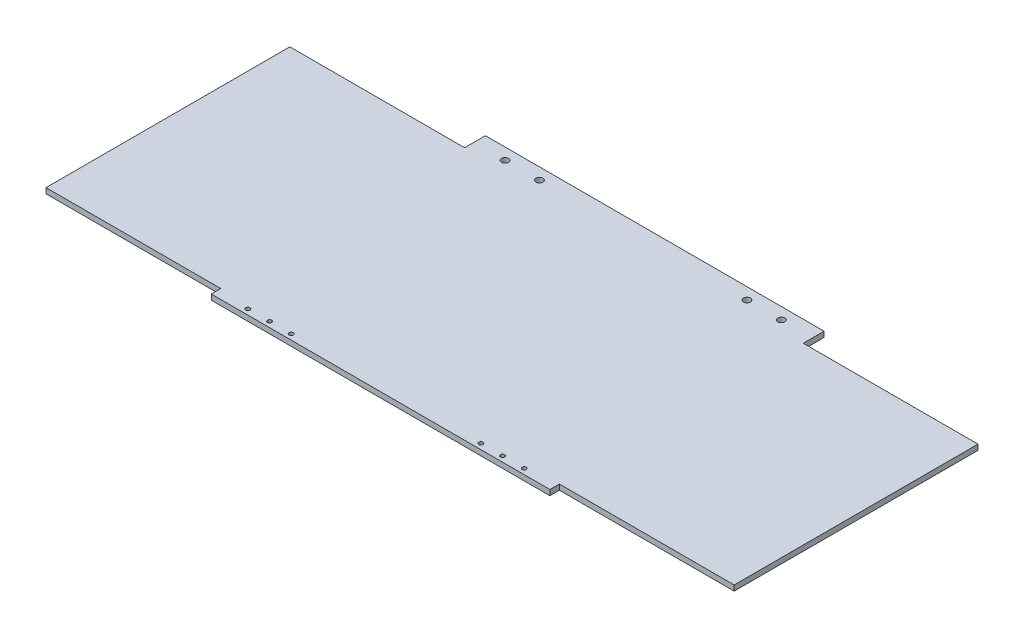
SolidWorks part; units mm, degrees
ref_plane "Front Plane" through (0, 0, 0) normal (0, 0, 1) x (1, 0, 0)
ref_plane "Top Plane" through (0, 0, 0) normal (0, 1, 0) x (1, 0, 0)
ref_plane "Right Plane" through (0, 0, 0) normal (1, 0, 0) x (0, 0, -1)
sketch "Sketch1" plane through (0, 0, 0) normal (0, 1, 0) x (1, 0, 0)
  line L0 (129, 0) -> (129, -7)
  line L1 (0, 0) -> (129, 0)
  line L2 (0, 0) -> (0, 180)
  line L3 (0, 180) -> (129, 180)
  line L4 (508, 0) -> (508, 180)
  line L5 (129, -7) -> (379, -7)
  line L6 (379, -7) -> (379, 0)
  line L7 (0, 90) -> (508, 90) construction
  line L8 (129, 180) -> (129, 195.398)
  line L9 (129, 195.398) -> (379, 195.398)
  line L10 (379, 195.398) -> (379, 180)
  line L11 (254, 195.398) -> (254, -38.1) construction
  line L12 (379, 0) -> (508, 0)
  line L13 (379, 180) -> (508, 180)
  line L14 (129, 186.858) -> (379, 186.858) construction
  line L15 (129, -3) -> (254, -3) construction
  circle A0 centre (152, 186.858) radius 2.564
  circle A1 centre (177.4, 186.858) radius 2.564
  circle A4 centre (152, -3) radius 1.54
  circle A5 centre (184, -3) radius 1.54
  circle A8 centre (330.6, 186.858) radius 2.564
  circle A9 centre (356, 186.858) radius 2.564
  circle A10 centre (168, -3) radius 1.54
  circle A11 centre (324, -3) radius 1.54
  circle A12 centre (340, -3) radius 1.54
  circle A13 centre (356, -3) radius 1.54
  point P10 (254, 90)
  dimension "D7" = 3.08
  dimension "D9" = 5.128
  dimension "D1" = 180
  dimension "D2" = 508
  dimension "D3" = 250
  dimension "D5" = 250
  dimension "D8" = 8.54
  dimension "D10" = 25.4
  dimension "D11" = 23
  dimension "D6" = 6.858
  dimension "D12" = 16
  dimension "D13" = 16
  dimension "D14" = 23
  dimension "D15" = 4
  dimension "D4" = 3
extrude "Boss-Extrude1" add sketch "Sketch1" along normal blind 4
equation "\"cf_tube_outer_diameter\"= 25mm"
equation "\"cf_tube_inner_diameter\" = 21mm"
equation "\"mid_plate_mid_to_top\" = 100mm"
equation "\"mid_plate_mid_to_bottom\" = 30mm"
equation "\"mid_plate_horizontal_spacing\"=250mm"
equation "\"cf_plate_thickness\" =4mm"
equation "\"mid_tube_length\" = 500mm"
equation "\"mid_plate_bottom_width\" = 180mm"
equation "\"D1@Sketch1\"=\"mid_plate_bottom_width\""
equation "\"D2@Sketch1\"=\"mid_tube_length\"+\"cf_plate_thickness\"*2"
equation "\"D1@Boss-Extrude1\"=\"cf_plate_thickness\""
equation "\"D5@Sketch1\"=\"mid_plate_horizontal_spacing\""
equation "\"D3@Sketch1\"=\"mid_plate_horizontal_spacing\""
